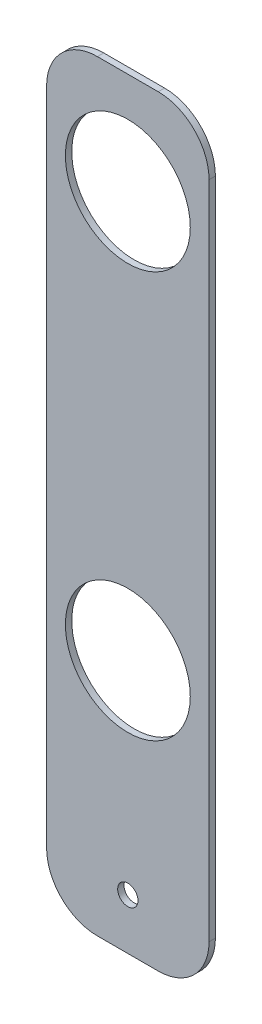
SolidWorks part; units mm, degrees
material "6061 Alloy"
ref_plane "Front Plane" through (0, 0, 0) normal (0, 0, 1) x (1, 0, 0)
ref_plane "Top Plane" through (0, 0, 0) normal (0, 1, 0) x (1, 0, 0)
ref_plane "Right Plane" through (0, 0, 0) normal (1, 0, 0) x (0, 0, -1)
sketch "Sketch1" plane through (0, 0, 0) normal (0, 0, 1) x (1, 0, 0)
  line L0 (0, 0) -> (0, -101.6) construction
  line L2 (-7.62, 25.4) -> (7.62, 25.4)
  line L3 (-20.32, 12.7) -> (-20.32, -152.4)
  line L4 (-7.62, -165.1) -> (7.62, -165.1)
  line L5 (20.32, 12.7) -> (20.32, -152.4)
  circle A0 centre (0, 0) radius 38.1 construction
  circle A1 centre (0, -101.6) radius 38.1 construction
  circle A2 centre (0, 0) radius 15.621
  circle A3 centre (0, -101.6) radius 15.621
  arc A4 (7.62, -165.1) -> (20.32, -152.4) centre (7.62, -152.4) ccw
  arc A5 (-20.32, -152.4) -> (-7.62, -165.1) centre (-7.62, -152.4) ccw
  arc A6 (7.62, 25.4) -> (20.32, 12.7) centre (7.62, 12.7) cw
  arc A7 (-7.62, 25.4) -> (-20.32, 12.7) centre (-7.62, 12.7) ccw
  circle A8 centre (0, -152.4) radius 2.54
  point P3 (0, 0)
  point P5 (0, -125.0992)
  point P20 (20.32, 25.4)
  point P23 (-20.32, 25.4)
  point P26 (0, 0)
  point P27 (0, 0)
  point P28 (0, -127)
  dimension "D2" = 76.2
  dimension "D3" = 76.2
  dimension "D4" = 31.242
  dimension "D5" = 31.242
  dimension "D10" = 12.7
  dimension "D11" = 5.08
  dimension "D1" = 101.6
  dimension "D6" = 40.64
  dimension "D7" = 20.32
  dimension "D8" = 25.4
  dimension "D9" = 63.5
extrude "Boss-Extrude1" add sketch "Sketch1" along normal blind 1.5875
